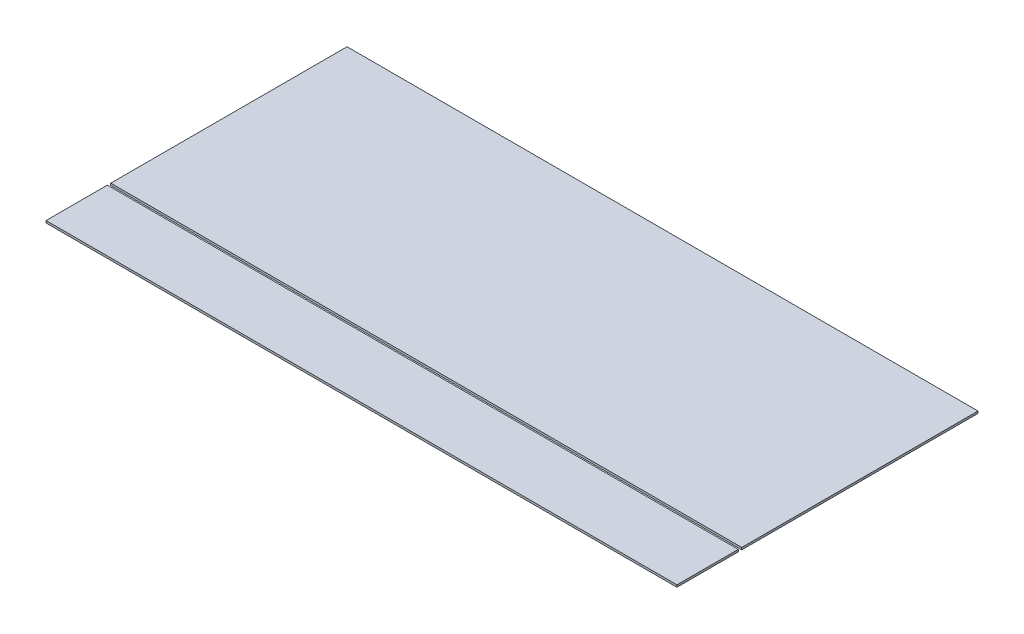
SolidWorks part; units mm, degrees
ref_plane "Front Plane" through (0, 0, 0) normal (0, 0, 1) x (1, 0, 0)
ref_plane "Top Plane" through (0, 0, 0) normal (0, 1, 0) x (1, 0, 0)
ref_plane "Right Plane" through (0, 0, 0) normal (1, 0, 0) x (0, 0, -1)
sketch "Sketch1" plane through (0, 0, 0) normal (0, 1, 0) x (1, 0, 0)
  line L1 (-736.6, -195.9) -> (736.6, -195.9)
  line L2 (-736.6, -195.9) -> (-736.6, 348.3)
  line L3 (-736.6, 348.3) -> (736.6, 348.3)
  line L4 (736.6, -195.9) -> (736.6, 348.3)
  line L5 (-736.6, -195.9) -> (736.6, 348.3) construction
  line L6 (-736.6, 348.3) -> (736.6, -195.9) construction
  line L11 (-736.6, -348.3) -> (736.6, -348.3)
  line L12 (-736.6, -348.3) -> (-736.6, -215.9)
  line L13 (-736.6, -215.9) -> (736.6, -215.9)
  line L14 (736.6, -348.3) -> (736.6, -215.9)
  point P0 (0, 0)
extrude "Boss-Extrude1" add sketch "Sketch1" along normal blind 2.5 and the other way blind 2.5
sketch "Sketch2" plane through (0, 0, 0) normal (0, 1, 0) x (1, 0, 0)
  line L5 (-736.6, 348.3) -> (736.6, 348.3)
  line L6 (-736.6, 348.3) -> (-736.6, -195.9)
  line L11 (-736.6, -195.9) -> (736.6, -195.9)
  line L12 (736.6, 348.3) -> (736.6, -195.9)
  line L13 (-736.6, -215.9) -> (736.6, -215.9)
  line L14 (-736.6, -215.9) -> (-736.6, -348.3)
  line L15 (-736.6, -348.3) -> (736.6, -348.3)
  line L16 (736.6, -215.9) -> (736.6, -348.3)
  line L17 (-742.6, 354.3) -> (742.6, 354.3)
  line L18 (-742.6, 354.3) -> (-742.6, -201.9)
  line L19 (-742.6, -201.9) -> (742.6, -201.9)
  line L20 (742.6, 354.3) -> (742.6, -201.9)
  line L21 (742.6, -354.3) -> (-742.6, -354.3)
  line L22 (742.6, -354.3) -> (742.6, -209.9)
  line L23 (742.6, -209.9) -> (-742.6, -209.9)
  line L24 (-742.6, -354.3) -> (-742.6, -209.9)
  dimension "D1" = 6
  dimension "D2" = 6
  dimension "D3" = 6
  dimension "D4" = 6
  dimension "D5" = 6
  dimension "D6" = 6
extrude "Boss-Extrude2" add sketch "Sketch2" along normal up to surface and the other way up to surface up to face at (0, 2.5, -76.2) other way up to face at (0, -2.5, -76.2)
